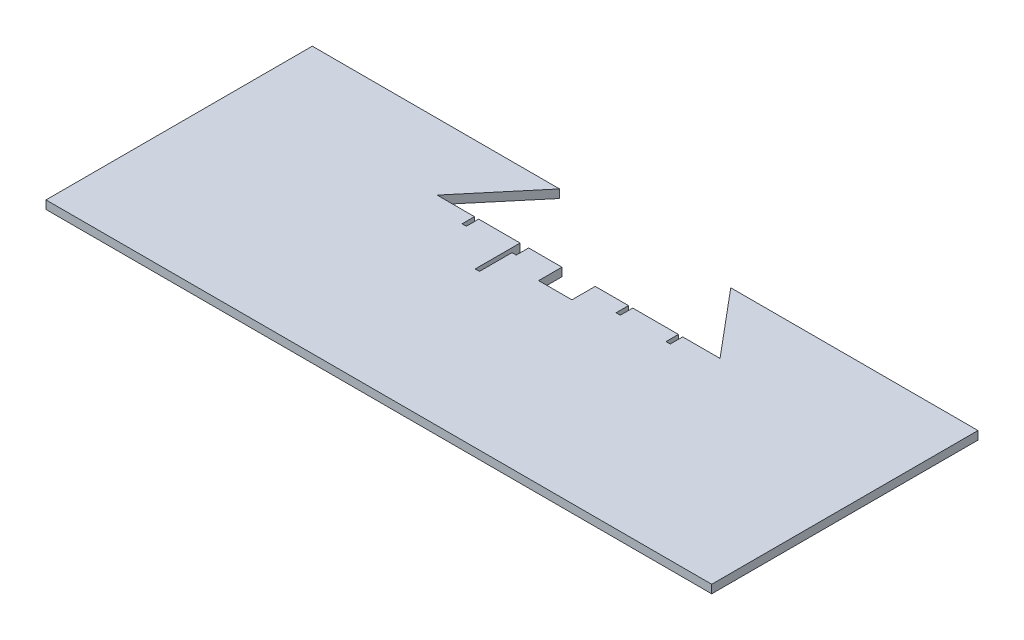
SolidWorks part; units mm, degrees
material "Depron"
ref_plane "Front Plane" through (0, 0, 0) normal (0, 0, 1) x (1, 0, 0)
ref_plane "Top Plane" through (0, 0, 0) normal (0, 1, 0) x (1, 0, 0)
ref_plane "Right Plane" through (0, 0, 0) normal (1, 0, 0) x (0, 0, -1)
sketch "Sketch1" plane through (0, 0, 0) normal (0, 1, 0) x (1, 0, 0)
  line L0 (32.6619, 101.6) -> (127, 101.6)
  line L1 (-127, 0) -> (127, 0)
  line L2 (-127, 0) -> (-127, 101.6)
  line L3 (-127, 101.6) -> (-32.6619, 101.6)
  line L4 (127, 0) -> (127, 101.6)
  line L5 (0, -898.4) -> (0, 49101.6) construction
  line L6 (-53.975, 76.2) -> (-32.6619, 101.6)
  line L7 (-53.975, 76.2) -> (53.975, 76.2)
  line L8 (53.975, 76.2) -> (32.6619, 101.6)
  line L9 (-1003.9539, 76.2) -> (48996.0461, 76.2) construction
  point P11 (0, 76.2)
  dimension "D1" = 101.6
  dimension "D2" = 254
  dimension "D4" = 107.95
  dimension "D6" = 25.4
  dimension "angle1" = 50
extrude "Boss-Extrude1" add sketch "Sketch1" along normal blind 3.175
sketch "Sketch2" plane through (0, 3.175, 0) normal (0, 1, 0) x (-1, 0, 0)
  line L0 (0, 0) -> (0, -134.62) construction
  line L1 (127, 0) -> (-127, 0) construction
  line L2 (-53.975, -76.2) -> (53.975, -76.2) construction
  line L3 (39.7256, -76.2) -> (38.1, -76.2)
  line L4 (39.7256, -76.2) -> (39.7256, -71.4756)
  line L5 (39.7256, -71.4756) -> (38.1, -71.4756)
  line L6 (38.1, -76.2) -> (38.1, -71.4756)
  line L7 (20.6756, -76.2) -> (19.05, -76.2)
  line L8 (-53.975, -76.2) -> (53.975, -76.2) construction
  line L9 (20.6756, -71.4756) -> (19.05, -71.4756)
  line L10 (19.05, -76.2) -> (19.05, -71.4756)
  line L11 (-19.05, -76.2) -> (-19.05, -71.4756)
  line L12 (-20.6756, -71.4756) -> (-19.05, -71.4756)
  line L13 (-20.6756, -76.2) -> (-20.6756, -71.4756)
  line L14 (-20.6756, -76.2) -> (-19.05, -76.2)
  line L15 (-38.1, -76.2) -> (-38.1, -71.4756)
  line L16 (-39.7256, -71.4756) -> (-38.1, -71.4756)
  line L17 (-39.7256, -76.2) -> (-39.7256, -71.4756)
  line L18 (-39.7256, -76.2) -> (-38.1, -76.2)
  line L19 (6.35, -76.2) -> (-6.35, -76.2)
  line L20 (20.6756, -76.2) -> (22.3012, -76.2)
  line L21 (20.6756, -71.4756) -> (20.6756, -59.055)
  line L22 (20.6756, -59.055) -> (22.3012, -59.055)
  line L23 (22.3012, -76.2) -> (22.3012, -59.055)
  line L24 (6.35, -76.2) -> (6.35, -67.31)
  line L25 (6.35, -67.31) -> (-6.35, -67.31)
  line L26 (-6.35, -76.2) -> (-6.35, -67.31)
  line L27 (-53.975, -76.2) -> (-51.3109, -79.375)
  line L28 (50.8, -80.9625) -> (57.15, -80.9625) construction
  line L29 (50.8, -80.9625) -> (50.8, -71.4375) construction
  line L30 (50.8, -71.4375) -> (57.15, -71.4375)
  line L31 (57.15, -80.9625) -> (57.15, -71.4375) construction
  line L32 (50.8, -80.9625) -> (57.15, -71.4375) construction
  line L33 (50.8, -71.4375) -> (57.15, -80.9625) construction
  line L34 (-50.8, -76.2) -> (-53.975, -76.2)
  line L35 (-50.8, -76.2) -> (-50.8, -71.4375)
  line L36 (-50.8, -71.4375) -> (-57.15, -71.4375)
  line L37 (53.975, -76.2) -> (32.6619, -101.6) construction
  line L38 (53.975, -76.2) -> (51.3109, -79.375)
  line L39 (51.3109, -79.375) -> (57.15, -79.375)
  line L40 (57.15, -79.375) -> (57.15, -71.4375)
  line L41 (50.8, -76.2) -> (50.8, -71.4375)
  line L42 (50.8, -76.2) -> (53.975, -76.2)
  line L43 (-57.15, -79.375) -> (-57.15, -71.4375)
  line L44 (-51.3109, -79.375) -> (-57.15, -79.375)
  point P31 (0, -67.31)
  point P32 (53.975, -76.2)
  line M6 (-53.975, -76.2) -> (53.975, -76.2)
  dimension "D1" = 1.6256
  dimension "D2" = 4.7244
  dimension "D3" = 1.6256
  dimension "D4" = 4.7244
  dimension "D5" = 1.6256
  dimension "D6" = 17.145
  dimension "D7" = 19.05
  dimension "D8" = 38.1
  dimension "D9" = 12.7
  dimension "D10" = 8.89
  dimension "D11" = 6.35
  dimension "D12" = 9.525
  dimension "D13" = 3.175
ref_plane "Center Plane" through (0, 0, 0) normal (1, 0, 0) x (0, 0, -1)
sketch "Sketch3" plane through (0, 3.175, 0) normal (0, 1, 0) x (1, 0, 0)
  line L0 (-38.9128, 71.4756) -> (-38.9128, 76.2)
  line L1 (-39.7256, 71.4756) -> (-38.1, 71.4756) construction
  line L2 (-39.7256, 76.2) -> (-38.1, 76.2) construction
  line L3 (-21.4884, 76.2) -> (-21.4884, 59.055)
  line L4 (-20.6756, 76.2) -> (-22.3012, 76.2) construction
  line L5 (-20.6756, 59.055) -> (-22.3012, 59.055) construction
  line L6 (-19.8628, 71.4756) -> (-19.8628, 76.2)
  line L7 (-20.6756, 71.4756) -> (-19.05, 71.4756) construction
  line L8 (-20.6756, 76.2) -> (-19.05, 76.2) construction
  line L9 (-6.35, 76.2) -> (-6.35, 67.31)
  line L10 (-6.35, 67.31) -> (6.35, 67.31)
  line L11 (6.35, 67.31) -> (6.35, 76.2)
  line L12 (19.8628, 71.4756) -> (19.8628, 76.2)
  line L13 (20.6756, 71.4756) -> (19.05, 71.4756) construction
  line L14 (20.6756, 76.2) -> (19.05, 76.2) construction
  line L15 (38.9128, 71.4756) -> (38.9128, 76.2)
  line L16 (39.7256, 71.4756) -> (38.1, 71.4756) construction
  line L17 (39.7256, 76.2) -> (38.1, 76.2) construction
extrude "Cut-Extrude1" cut sketch "Sketch2" against normal up to surface (3.175 mm away) contours L6 L4 L5 M6 | L23 L22 L21 L9 L10 M6 | L26 L24 L25 M6 | L13 L11 L12 M6 | L17 L15 L16 M6 region at (38.9128, 3.175, -73.8378) region at (19.8628, 3.175, -73.8378) region at (0, 3.175, -71.755) region at (-21.1372, 3.175, -68.9691) region at (-38.9128, 3.175, -73.8378) up to face at (0, 0, -69.85)
